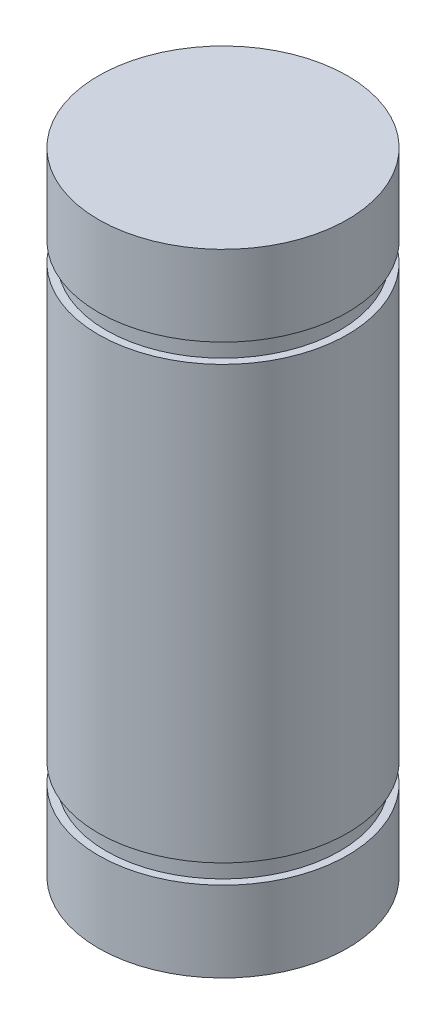
SolidWorks part; units mm, degrees
ref_plane "Front Plane" through (0, 0, 0) normal (0, 0, 1) x (1, 0, 0)
ref_plane "Top Plane" through (0, 0, 0) normal (0, 1, 0) x (1, 0, 0)
ref_plane "Right Plane" through (0, 0, 0) normal (1, 0, 0) x (0, 0, -1)
sketch "Sketch1" plane through (0, 0, 0) normal (0, 1, 0) x (1, 0, 0)
  circle A0 centre (0, 0) radius 4.7625
  dimension "D1" = 9.525
extrude "Boss-Extrude1" add sketch "Sketch1" against normal blind 8.255 and the other way blind 8.255
sketch3d "3DSketch2" plane through (0, 0, 0) normal (0, 0, 1) x (1, 0, 0)
  dimension "D1" = 0.7366
sketch "Sketch2" plane through (0, 8.255, 0) normal (0, 1, 0) x (1, 0, 0)
  circle A0 centre (0, 0) radius 4.7625
  dimension "D1" = 9.525
extrude "Boss-Extrude2" add sketch "Sketch2" along normal blind 3.81 contours A0
sketch3d "3DSketch3" plane through (0, 0, 0) normal (0, 0, 1) x (1, 0, 0)
  dimension "D1" = 0.7366
sketch "Sketch3" plane through (0, -8.255, 0) normal (0, -1, 0) x (-1, 0, 0)
  circle A0 centre (0, 0) radius 4.7625
  dimension "D1" = 9.525
extrude "Boss-Extrude3" add sketch "Sketch3" along normal blind 3.81 contours A0
sketch "Sketch4" plane through (0, -8.9916, 0) normal (0, -1, 0) x (-1, 0, 0)
  circle A0 centre (0, 0) radius 5.08
  dimension "D1" = 10.16
extrude "Cut-Extrude1" cut sketch "Sketch4" against normal blind 0.7366
sketch "Sketch5" plane through (0, 8.9916, 0) normal (0, 1, 0) x (1, 0, 0)
  circle A0 centre (0, 0) radius 5.08
  dimension "D1" = 10.16
extrude "Cut-Extrude2" cut sketch "Sketch5" against normal blind 0.7366
sketch "Sketch6" plane through (0, -8.9916, 0) normal (0, 1, 0) x (1, 0, 0)
  circle A0 centre (0, 0) radius 4.4704
  dimension "D1" = 8.9408
extrude "Boss-Extrude4" add sketch "Sketch6" along normal up to surface (0.7366 mm away) up to face at (0, -8.255, -4.7625)
sketch "Sketch7" plane through (0, 8.255, 0) normal (0, 1, 0) x (1, 0, 0)
  circle A0 centre (0, 0) radius 4.4704
  dimension "D1" = 8.9408
extrude "Boss-Extrude5" add sketch "Sketch7" along normal up to surface (0.7366 mm away) up to face at (0, 8.9916, 4.7625)
